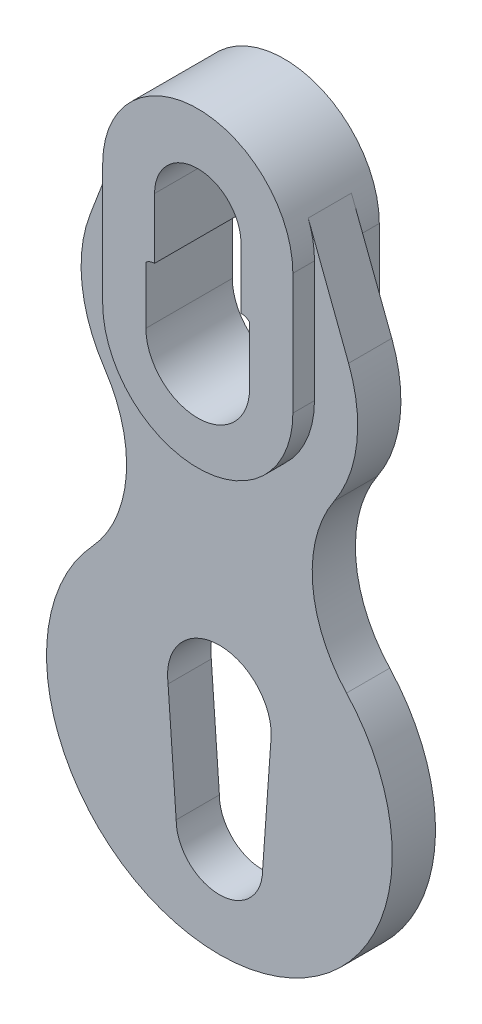
SolidWorks part; units mm, degrees
ref_plane "Front Plane" through (0, 0, 0) normal (0, 0, 1) x (1, 0, 0)
ref_plane "Top Plane" through (0, 0, 0) normal (0, 1, 0) x (1, 0, 0)
ref_plane "Right Plane" through (0, 0, 0) normal (1, 0, 0) x (0, 0, -1)
sketch "Sketch1" plane through (0, 0, 0) normal (0, 0, 1) x (1, 0, 0)
  line L0 (0, 0) -> (0, 54459.227) construction
  line L1 (0, 0) -> (54459.227, 0) construction
  line L2 (-12, 10) -> (-10, -18)
  line L3 (12, 10) -> (10, -18)
  line L4 (-29.8896, 93.4286) -> (-20.5491, 117.8571)
  line L5 (29.8896, 93.4286) -> (20.5491, 117.8571)
  line L6 (-12, 95.2361) -> (-12, 82)
  line L7 (10, 96) -> (10, 110)
  line L8 (-10, 96) -> (-10, 110)
  line L9 (12, 95.2361) -> (12, 82)
  line L10 (-22, 110) -> (-22, 82)
  line L11 (22, 110) -> (22, 82)
  arc A0 (-29.4135, 27.108) -> (29.4135, 27.108) centre (0, 0) ccw
  arc A1 (11.8782, 8.2944) -> (-11.8782, 8.2944) centre (0, 10) ccw
  arc A2 (-10, -18) -> (10, -18) centre (0, -18) ccw
  arc A3 (-12, 82) -> (12, 82) centre (0, 82) ccw
  arc A4 (-22, 82) -> (22, 82) centre (0, 82) ccw
  arc A5 (10, 110) -> (-10, 110) centre (0, 110) ccw
  arc A7 (26.5671, 64.1621) -> (29.8896, 93.4286) centre (0, 82) ccw
  arc A8 (-26.5671, 64.1621) -> (-29.4135, 27.108) centre (-51.4737, 47.439) cw
  arc A9 (26.5671, 64.1621) -> (29.4135, 27.108) centre (51.4737, 47.439) ccw
  arc A10 (-10, 96) -> (-12, 95.2361) centre (-10, 93) ccw
  arc A11 (10, 96) -> (12, 95.2361) centre (10, 93) cw
  arc A12 (-29.8896, 93.4286) -> (-26.5671, 64.1621) centre (0, 82) ccw
  arc A13 (22, 110) -> (-22, 110) centre (0, 110) ccw
  point P6 (0, 0)
  dimension "D1" = 80
  dimension "D2" = 24
  dimension "D3" = 20
  dimension "D6" = 28
  dimension "D7" = 22
  dimension "D8" = 20
  dimension "D9" = 24
  dimension "D10" = 44
  dimension "D12" = 64
  dimension "D13" = 30
  dimension "D14" = 3
  dimension "D4" = 10
  dimension "D5" = 28
  dimension "D11" = 128
  dimension "D15" = 14
extrude "Boss-Extrude1" add sketch "Sketch1" along normal mid plane 20 contours L11 A13 L10 A4 L7 A11 L9 A3 L6 A10 L8 A5 region at (0, 131.1562, 0)
extrude "Boss-Extrude2" add sketch "Sketch1<3>" along normal mid plane 10 contours A13 L11 A4 L10 L4 A12 A8 A0 A9 A7 L5 A2 L2 A1 L3 region at (-23.5663, 105.0108, 0)
sketch "Sketch1<3>" plane through (0, 0, 0) normal (0, 0, 1) x (1, 0, 0) same geometry as "Sketch1"
